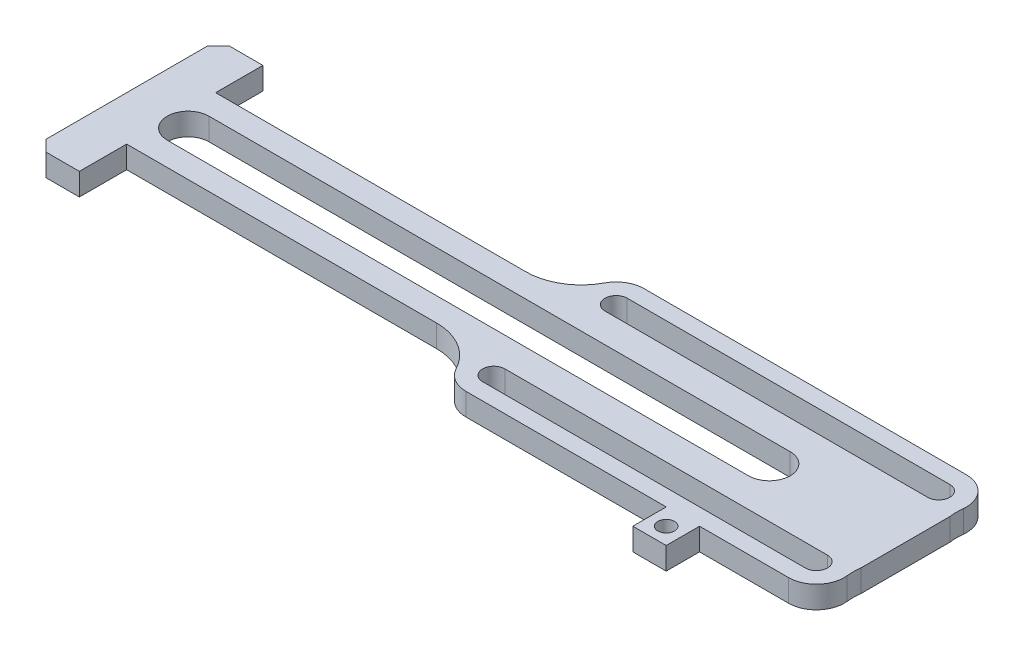
SolidWorks part; units mm, degrees
ref_plane "Спереди" through (0, 0, 0) normal (0, 0, 1) x (1, 0, 0)
ref_plane "Сверху" through (0, 0, 0) normal (0, 1, 0) x (1, 0, 0)
ref_plane "Справа" through (0, 0, 0) normal (1, 0, 0) x (0, 0, -1)
sketch "Эскиз1" plane through (0, 0, 0) normal (0, 1, 0) x (1, 0, 0)
  line L0 (0, 0) -> (-140, 0) construction
  line L1 (-140, -14.5) -> (-140, 14.5)
  line L2 (-140, 14.5) -> (-138, 16.5)
  line L3 (-138, 16.5) -> (-132, 16.5)
  line L4 (-132, 16.5) -> (-132, 8)
  line L5 (-132, 8) -> (0, 8)
  line L6 (0, 8) -> (0, -8)
  line L7 (-132, -8) -> (0, -8)
  line L8 (-132, -16.5) -> (-132, -8)
  line L9 (-138, -16.5) -> (-132, -16.5)
  line L10 (-140, -14.5) -> (-138, -16.5)
  dimension "D1" = 33
  dimension "D2" = 135
  dimension "D3" = 8
  dimension "D4" = 6
  dimension "D5" = 140
  dimension "D6" = 16
extrude "Бобышка-Вытянуть1" add sketch "Эскиз1" along normal blind 4
sketch "Эскиз2" plane through (0, 0, 0) normal (0, -1, 0) x (1, 0, 0)
  line L0 (0, 0) -> (-174.855, 0) construction
  line L1 (-63, 11) -> (-5, 11) construction
  line L2 (-63, 13) -> (-5, 13)
  line L3 (-63, 9) -> (-5, 9)
  line L4 (-63, 11) -> (-5, 11) construction
  line L5 (-63, 16) -> (-5, 16)
  line L6 (-63, 6) -> (-5, 6)
  line L8 (-63, -11) -> (-5, -11) construction
  line L9 (-63, -13) -> (-5, -13)
  line L10 (-63, -9) -> (-5, -9)
  line L11 (-63, -11) -> (-5, -11) construction
  line L12 (-63, -16) -> (-5, -16)
  line L13 (-63, -6) -> (-5, -6)
  arc A0 (-63, 13) -> (-63, 9) centre (-63, 11) ccw
  arc A1 (-5, 9) -> (-5, 13) centre (-5, 11) ccw
  arc A2 (-63, 16) -> (-63, 6) centre (-63, 11) ccw
  arc A3 (-5, 6) -> (-5, 16) centre (-5, 11) ccw
  arc A4 (-63, -13) -> (-63, -9) centre (-63, -11) cw
  arc A5 (-5, -9) -> (-5, -13) centre (-5, -11) cw
  arc A6 (-63, -16) -> (-63, -6) centre (-63, -11) cw
  arc A7 (-5, -6) -> (-5, -16) centre (-5, -11) cw
  point P5 (-34, 11)
  point P11 (-34, 11)
  point P21 (-34, -11)
  point P28 (-34, -11)
  dimension "D1" = 4
  dimension "D2" = 10
  dimension "D3" = 58
  dimension "D4" = 22
  dimension "D5" = 5
extrude "Бобышка-Вытянуть2" add sketch "Эскиз2" against normal up to surface (4 mm away) up to face at (-108.4, 4, 0)
fillet "Скругление1" radius 10 4 edges at (-1, 2, 8) (-1, 2, -8) (-67, 2, -8) (-67, 2, 8)
sketch "Эскиз3" plane through (0, 0, 0) normal (0, -1, 0) x (1, 0, 0)
  line L0 (-24.4476, 3.7538) -> (-128.9506, 3.7538)
  line L1 (-128.9506, -3.7462) -> (-24.4476, -3.7462)
  line L2 (-24.4476, 1.5038) -> (-128.9506, 1.5038)
  line L3 (-128.9506, -1.4962) -> (-24.4476, -1.4962)
  line L4 (-24.4476, 1.5038) -> (-128.9506, 1.5038) construction
  line L5 (-128.9506, -1.4962) -> (-24.4476, -1.4962) construction
  arc A0 (-128.9506, 3.7538) -> (-128.9506, -3.7462) centre (-128.9506, 0.0038) ccw
  arc A1 (-24.4476, -3.7462) -> (-24.4476, 3.7538) centre (-24.4476, 0.0038) ccw
  arc A2 (-128.9506, 1.5038) -> (-128.9506, -1.4962) centre (-128.9506, 0.0038) ccw
  arc A3 (-24.4476, -1.4962) -> (-24.4476, 1.5038) centre (-24.4476, 0.0038) ccw
  arc A4 (-128.9506, 1.5038) -> (-128.9506, -1.4962) centre (-128.9506, 0.0038) ccw construction
  arc A5 (-24.4476, -1.4962) -> (-24.4476, 1.5038) centre (-24.4476, 0.0038) ccw construction
  dimension "D3" = 7.5
  dimension "D1" = 0
  dimension "D2" = 2.25
extrude "Вырез-Вытянуть1" cut sketch "Эскиз3" against normal through all
sketch "Эскиз4" plane through (0, 4, 0) normal (0, 1, 0) x (1, 0, 0)
  line L1 (-21, -22) -> (-27, -22)
  line L2 (-21, -22) -> (-21, -16)
  line L3 (-21, -16) -> (-27, -16)
  line L4 (-27, -22) -> (-27, -16)
  line L5 (-21, -22) -> (-27, -16) construction
  line L6 (-21, -16) -> (-27, -22) construction
  line L7 (-63, -16) -> (-5, -16) construction
  line L8 (0, -8) -> (0, 8) construction
  point P0 (-24, -19)
  dimension "D1" = 6
  dimension "D2" = 6
  dimension "D3" = 21
extrude "Бобышка-Вытянуть7" add sketch "Эскиз4" against normal blind 4
sketch "Эскиз6" plane through (0, 4, 0) normal (0, 1, 0) x (1, 0, 0)
  line L0 (-27, -16) -> (-21, -22) construction
  circle A0 centre (-24, -19) radius 1.5
  dimension "D1" = 3
extrude "Вырез-Вытянуть4" cut sketch "Эскиз6" against normal through all
